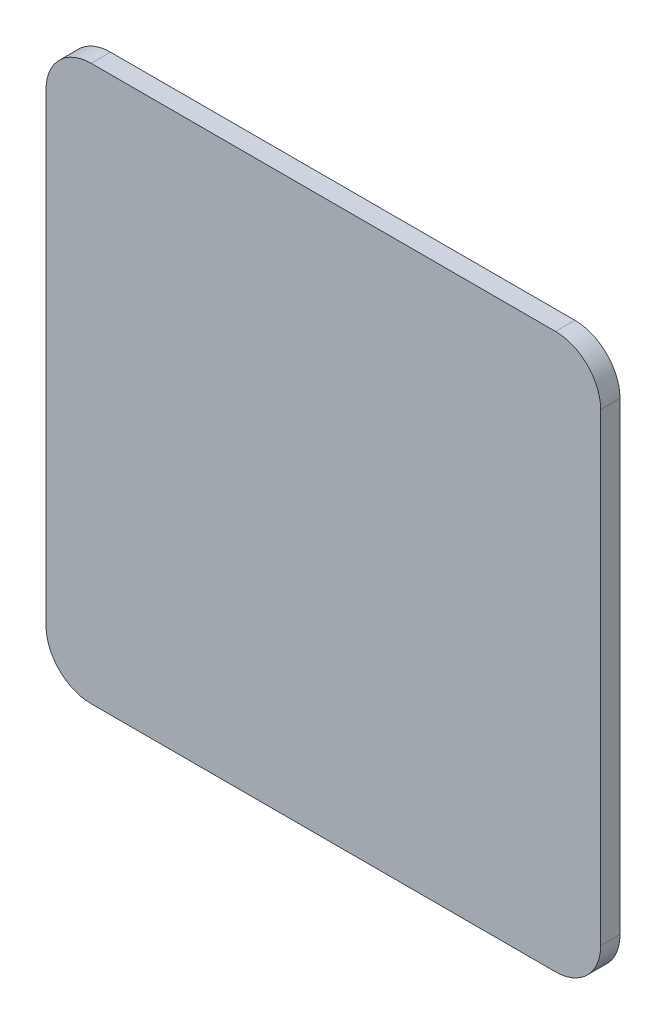
SolidWorks part; units mm, degrees
material "ABS PC"
ref_plane "Front Plane" through (0, 0, 0) normal (0, 0, 1) x (1, 0, 0)
ref_plane "Top Plane" through (0, 0, 0) normal (0, 1, 0) x (1, 0, 0)
ref_plane "Right Plane" through (0, 0, 0) normal (1, 0, 0) x (0, 0, -1)
sketch "Sketch1" plane through (0, 0, 0) normal (0, 0, 1) x (1, 0, 0)
  line L1 (-43, -43) -> (43, -43)
  line L2 (-43, -43) -> (-43, 43)
  line L3 (-43, 43) -> (43, 43)
  line L4 (43, -43) -> (43, 43)
  line L5 (-43, -43) -> (43, 43) construction
  line L6 (-43, 43) -> (43, -43) construction
  point P0 (0, 0)
  dimension "D1" = 86
  dimension "D2" = 86
extrude "Boss-Extrude1" add sketch "Sketch1" along normal blind 3
fillet "Fillet1" radius 7 4 edges at (-43, 43, 1.5) (-43, -43, 1.5) (43, -43, 1.5) (43, 43, 1.5)
